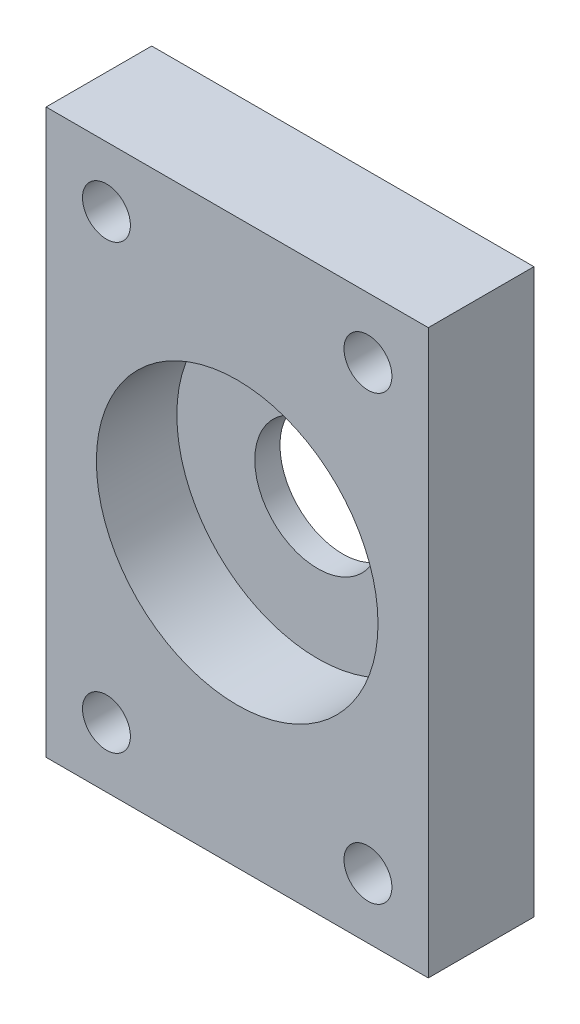
SolidWorks part; units mm, degrees
ref_plane "Alzado" through (0, 0, 0) normal (0, 0, 1) x (1, 0, 0)
ref_plane "Planta" through (0, 0, 0) normal (0, 1, 0) x (1, 0, 0)
ref_plane "Vista lateral" through (0, 0, 0) normal (1, 0, 0) x (0, 0, -1)
sketch "Croquis1" plane through (0, 0, 0) normal (0, 0, 1) x (1, 0, 0)
  circle A0 centre (0, 0) radius 14
  circle A1 centre (0, 0) radius 18
  dimension "D1" = 28
  dimension "D2" = 4
extrude "Saliente-Extruir1" add sketch "Croquis1" along normal blind 8
sketch "Croquis2" plane through (0, 0, 0) normal (0, 0, -1) x (-1, 0, 0)
  line L1 (-19, -28) -> (19, -28)
  line L2 (-19, -28) -> (-19, 28)
  line L3 (-19, 28) -> (19, 28)
  line L4 (19, -28) -> (19, 28)
  line L5 (-19, -28) -> (19, 28) construction
  line L6 (-19, 28) -> (19, -28) construction
  circle A0 centre (0, 0) radius 18 construction
  circle A1 centre (0, 0) radius 18
  point P0 (0, 0)
  dimension "D1" = 38
  dimension "D2" = 56
extrude "Saliente-Extruir2" add sketch "Croquis2" against normal blind 8
sketch "Croquis5" plane through (0, 0, 0) normal (0, 0, -1) x (-1, 0, 0)
  line L4 (19, -28) -> (19, 28)
  line L5 (19, 28) -> (-19, 28)
  line L6 (-19, 28) -> (-19, -28)
  line L7 (-19, -28) -> (19, -28)
  line L8 (19, -28) -> (19, 28)
  line L9 (19, 28) -> (-19, 28)
  line L10 (-19, 28) -> (-19, -28)
  line L11 (-19, -28) -> (19, -28)
  circle A0 centre (0, 0) radius 6.25
  dimension "D2" = 12.5
  dimension "D1" = 0
extrude "Saliente-Extruir3" add sketch "Croquis5" along normal blind 2.5
sketch "Croquis7" plane through (0, 0, -2.5) normal (0, 0, -1) x (-1, 0, 0)
  line L0 (25.83, 0) -> (-30.4698, 0) construction
  line L1 (0, 25.0731) -> (0, -24.2875) construction
  line L2 (19, 28) -> (-19, 28) construction
  line L3 (-19, 28) -> (-19, -28) construction
  circle A0 centre (-13, 22) radius 2.3813
  circle A1 centre (13, 22) radius 2.3813
  circle A2 centre (13, -22) radius 2.3813
  circle A3 centre (-13, -22) radius 2.3813
  dimension "D3" = 4.7625
  dimension "D1" = 6
  dimension "D2" = 6
extrude "Cortar-Extruir3" cut sketch "Croquis7" against normal through all
